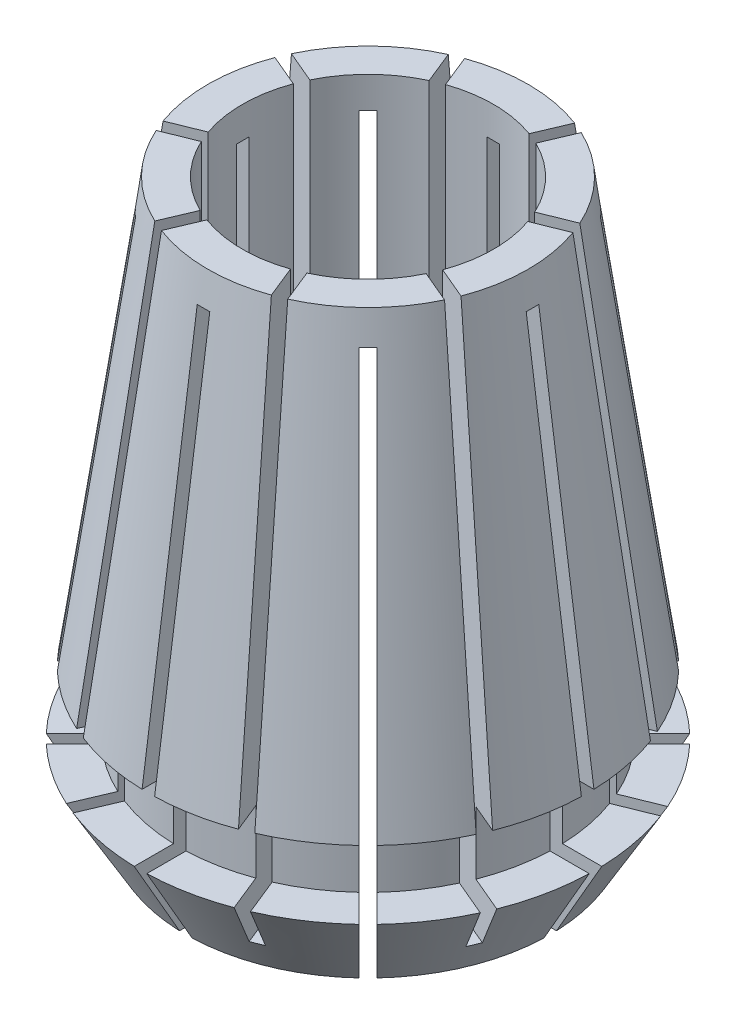
SolidWorks part; units mm, degrees
material "Steel"
ref_plane "Front Plane" through (0, 0, 0) normal (0, 0, 1) x (1, 0, 0)
ref_plane "Top Plane" through (0, 0, 0) normal (0, 1, 0) x (1, 0, 0)
ref_plane "Right Plane" through (0, 0, 0) normal (1, 0, 0) x (0, 0, -1)
sketch "Sketch1" plane through (0, 0, 0) normal (0, 0, 1) x (1, 0, 0)
  line L0 (0, 0) -> (0, 41.5693) construction
  line L1 (0, 0) -> (33.0314, 0) construction
  line L2 (-4, -4.5) -> (-4, 13.5)
  line L5 (-4, 13.5) -> (-5.1027, 13.5)
  line L6 (-5.1027, 13.5) -> (-7, 0)
  line L7 (-7, 0) -> (-6, 0)
  line L8 (-6, 0) -> (-6, -2)
  line L9 (-6, -2) -> (-7.25, -2)
  line L10 (-7.25, -2) -> (-5.8066, -4.5)
  line L11 (-5.8066, -4.5) -> (-4, -4.5)
  dimension "D1" = 8
  dimension "D2" = 30
  dimension "D3" = 14.5
  dimension "D4" = 2.5
  dimension "D6" = 8
  dimension "D7" = 14
  dimension "D8" = 2
  dimension "D10" = 12
  dimension "D11" = 18
revolve "Rotation1" add sketch "Sketch1" angle 360 about L0
sketch "Sketch2" plane through (0, -4.5, 0) normal (0, -1, 0) x (1, 0, 0)
  line L0 (0, 0) -> (0, 3.7936) construction
  line L2 (-0.2, 7.25) -> (0.2, 7.25)
  line L3 (-0.2, 7.25) -> (-0.2, 3.995)
  line L4 (-0.2, 3.995) -> (0.2, 3.995)
  line L5 (0.2, 7.25) -> (0.2, 3.995)
  circle A0 centre (0, 0) radius 7.25 construction
  circle A1 centre (0, 0) radius 4 construction
  dimension "D1" = 0.2
  dimension "D2" = 0.2
extrude "Extruded Cut1" cut sketch "Sketch2" against normal blind 17
ref_axis "Axis1" through (0, 13.5, 0) along (0, -1, 0)
sketch "Sketch3" plane through (0, 13.5, 0) normal (0, 1, 0) x (1, 0, 0)
  line L0 (0, 0) -> (0, 3.6628) construction
  line L1 (0, 0) -> (-1.6514, 4.0874) construction
  line L2 (-0.1854, -0.0749) -> (-2.9013, 6.6472)
  line L3 (-2.9013, 6.6472) -> (-2.5305, 6.797)
  line L4 (-2.5305, 6.797) -> (0.1854, 0.0749)
  line L5 (0.1854, 0.0749) -> (-0.1854, -0.0749)
  arc A0 (0.2, -7.2472) -> (-0.2, -7.2472) centre (0, 0) ccw construction
  dimension "D1" = 22
  dimension "D2" = 0.2
  dimension "D3" = 0.2
extrude "Extruded Cut2" cut sketch "Sketch3" against normal blind 17
pattern_circular "Circular Pattern1" count 8 over 360 about axis through (0, 13.5, 0) along (0, -1, 0) of "Extruded Cut1", "Extruded Cut2"
